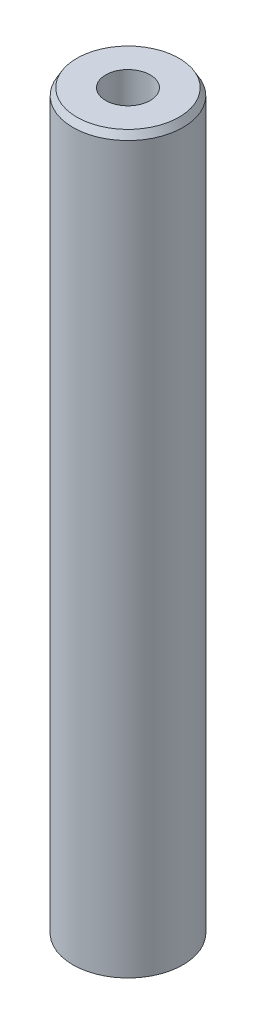
SolidWorks part; units mm, degrees
ref_plane "Front Plane" through (0, 0, 0) normal (0, 0, 1) x (1, 0, 0)
ref_plane "Top Plane" through (0, 0, 0) normal (0, 1, 0) x (1, 0, 0)
ref_plane "Right Plane" through (0, 0, 0) normal (1, 0, 0) x (0, 0, -1)
sketch "Sketch1" plane through (0, 0, 0) normal (0, 1, 0) x (1, 0, 0)
  circle A0 centre (0, 0) radius 10
  dimension "SHAFT_OD" = 20
extrude "Boss-Extrude1" add sketch "Sketch1" along normal blind 133.7034
sketch "Sketch2" plane through (0, 0, 0) normal (0, 1, 0) x (1, 0, 0)
  circle A0 centre (0, 0) radius 4.0423
  dimension "BORE_D" = 8.0847
extrude "Cut-Extrude1" cut sketch "Sketch2" along normal through all
chamfer "Chamfer1" distance 1.2514 angle 30 2 edges at (0, 133.7034, 10) (0, 0, 10) first distance on face at (0, 133.7034, 10) first distance on face at (0, 0, 4.0423)
